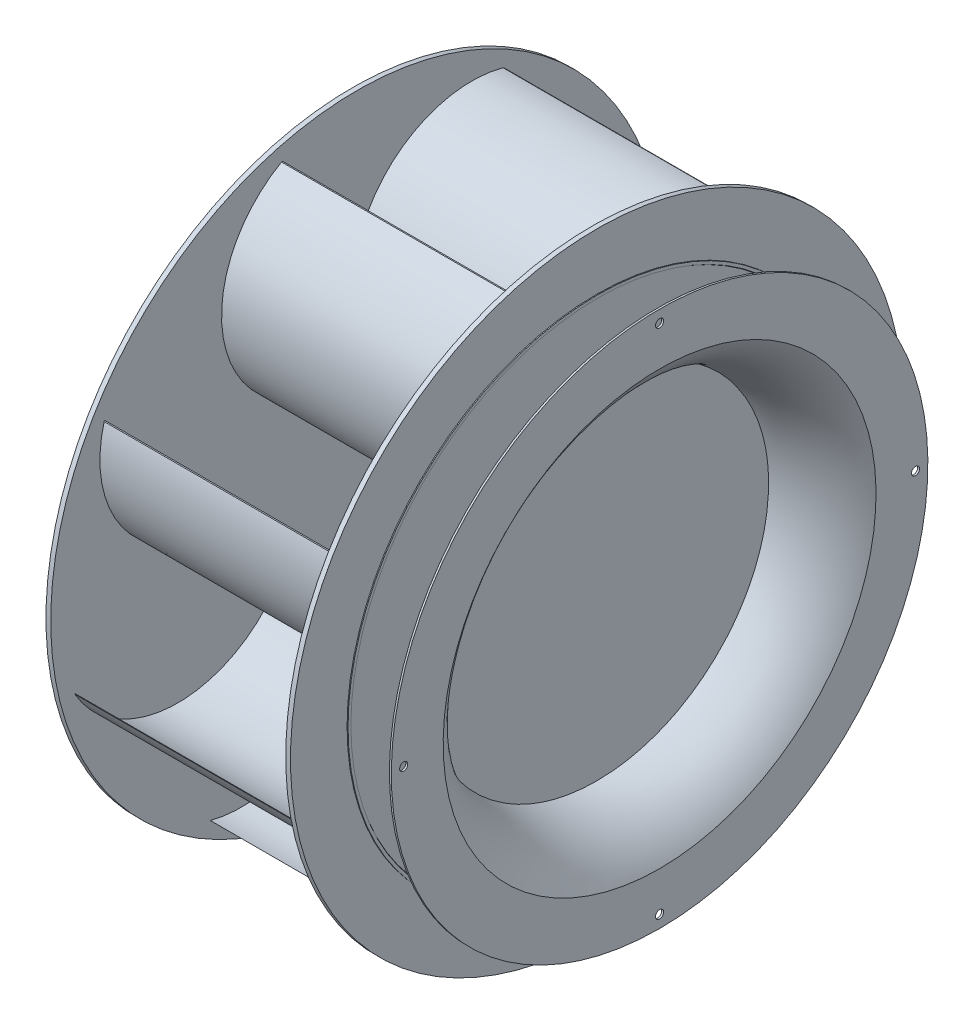
SolidWorks part; units mm, degrees
ref_plane "Front Plane" through (0, 0, 0) normal (0, 0, 1) x (1, 0, 0)
ref_plane "Top Plane" through (0, 0, 0) normal (0, 1, 0) x (1, 0, 0)
ref_plane "Right Plane" through (0, 0, 0) normal (1, 0, 0) x (0, 0, -1)
sketch "Sketch1" plane through (0, 0, 0) normal (0, 0, 1) x (1, 0, 0)
  line L0 (0, 0) -> (831.9083, 0) construction
  line L1 (0, 0) -> (0, 109)
  line L2 (5, 114) -> (70, 114)
  line L3 (70, 114) -> (70, 138)
  line L4 (70, 138) -> (90, 138)
  line L5 (90, 138) -> (90, 98)
  line L6 (90, 98) -> (95, 98)
  line L7 (95, 98) -> (95, 133)
  line L8 (95, 133) -> (105, 133)
  line L9 (105, 133) -> (105, 98)
  line L10 (105, 98) -> (129, 98)
  line L11 (129, 98) -> (129, 0)
  line L12 (129, 0) -> (0, 0)
  arc A0 (5, 114) -> (0, 109) centre (5, 109) ccw
  point P16 (0, 114)
  dimension "D10" = 5
  dimension "D1" = 114
  dimension "D2" = 24
  dimension "D3" = 70
  dimension "D4" = 40
  dimension "D5" = 35
  dimension "D6" = 5
  dimension "D7" = 20
  dimension "D8" = 10
  dimension "D9" = 59
revolve "Revolve1" add sketch "Sketch1" angle 360 about L0
sketch "Sketch2" plane through (129, 0, 0) normal (1, 0, 0) x (0, 0, -1)
  circle A0 centre (0, 0) radius 322
  dimension "D1" = 644
extrude "Extrude1" add sketch "Sketch2" along normal blind 5
sketch "Sketch9" plane through (129, 0, 0) normal (-1, 0, 0) x (0, 0, 1)
  circle A0 centre (0, 0) radius 317
  circle A1 centre (0, 0) radius 100
  circle A2 centre (0, 0) radius 322 construction
  dimension "D1" = 5
  dimension "D2" = 200
extrude "Extrude7" cut sketch "Sketch9" against normal blind 3
ref_plane "Plane1" through (381, 0, 0) normal (1, 0, 0) x (0, 0, -1)
sketch "Sketch3" plane through (381, 0, 0) normal (1, 0, 0) x (0, 0, -1)
  circle A0 centre (0, 0) radius 322
  dimension "D1" = 644
extrude "Extrude2" add sketch "Sketch3" along normal blind 5 separate body
sketch "Sketch4" plane through (134, 0, 0) normal (1, 0, 0) x (0, 0, -1)
  line L0 (0, 0) -> (0, 307) construction
  line L1 (0, 0) -> (161, 278.8602) construction
  line L2 (0, 112.5) -> (0.866, 112)
  line L3 (153.5, 265.8698) -> (154.366, 265.3698)
  circle A0 centre (0, 0) radius 307 construction
  circle A1 centre (0, 0) radius 322 construction
  circle A2 centre (0, 0) radius 112.5 construction
  arc A3 (0, 112.5) -> (153.5, 265.8698) centre (120.6282, 145.2694) cw
  arc A4 (0.866, 112) -> (154.366, 265.3698) centre (121.4942, 144.7694) cw
  dimension "D1" = 15
  dimension "D2" = 225
  dimension "D6" = 125
  dimension "D7" = 125
  dimension "D3" = 30
  dimension "D4" = 60
  dimension "D5" = 1
extrude "Extrude3" add sketch "Sketch4" along normal up to surface (252 mm away) up to face at (386, 0, -322)
ref_axis "Axis1" through (253.5503, 0, 0) along (-1, 0, 0)
pattern_circular "CirPattern1" count 8 over 360 about axis through (253.5503, 0, 0) along (-1, 0, 0) of "Extrude3"
sketch "Sketch5" plane through (0, 0, 0) normal (0, 0, 1) x (1, 0, 0)
  line L0 (0, 0) -> (527.2916, 0) construction
  line L1 (253.5503, 0) -> (75.411, 0) construction
  line L2 (386, 262.5) -> (387, 262.5)
  line L3 (387, 262.5) -> (387, 259.5)
  line L4 (386, 262.5) -> (386, 259.5)
  line L5 (354, 182.5) -> (354, 181.5)
  line L6 (70, 138) -> (70, -138) construction
  line L7 (386, -322) -> (386, 322) construction
  arc A0 (387, 259.5) -> (354, 182.5) centre (422.05, 198.9071) ccw
  arc A1 (386, 259.5) -> (354, 181.5) centre (421.7019, 199.2889) ccw
  dimension "D7" = 70
  dimension "D8" = 70
  dimension "D1" = 181.5
  dimension "D2" = 1
  dimension "D3" = 1
  dimension "D4" = 3
  dimension "D5" = 262.5
  dimension "D6" = 284
revolve "Revolve2" add sketch "Sketch5" angle 360 about L0
ref_plane "Plane3" through (452, 0, 0) normal (1, 0, 0) x (0, 0, -1)
sketch "Sketch6" plane through (0, 0, 0) normal (0, 0, 1) x (1, 0, 0)
  line L0 (452, 282) -> (450, 282)
  line L1 (452, -251.35) -> (452, 251.35) construction
  line L2 (450, 282) -> (450, 227.5)
  line L3 (0, 0) -> (615.1417, 0) construction
  line L4 (0, 114) -> (0, -114) construction
  line L5 (253.5503, 0) -> (75.411, 0) construction
  line L6 (452, 282) -> (452, 227.5)
  line L7 (348, 181.5) -> (352, 181.5)
  line L8 (348, 181.5) -> (348, 179.5)
  line L9 (348, 179.5) -> (352, 179.5)
  arc A0 (352, 181.5) -> (450, 227.5) centre (365.2724, 280.6153) ccw
  arc A1 (352, 179.5) -> (452, 227.5) centre (365.9922, 278.5163) ccw
  dimension "D7" = 100
  dimension "D8" = 100
  dimension "D1" = 282
  dimension "D2" = 2
  dimension "D3" = 227.5
  dimension "D4" = 104
  dimension "D5" = 181.5
  dimension "D6" = 4
revolve "Revolve3" add sketch "Sketch6" angle 360 about L3
sketch "Sketch7" plane through (452, 0, 0) normal (1, 0, 0) x (0, 0, -1)
  line L0 (0, 0) -> (0, 269) construction
  circle A0 centre (0, 0) radius 269 construction
  circle A1 centre (0, 269) radius 4.25
  dimension "D1" = 538
  dimension "D2" = 8.5
extrude "Extrude5" cut sketch "Sketch7" against normal blind 5
pattern_circular "CirPattern2" count 4 over 360 about axis through (253.5503, 0, 0) along (-1, 0, 0) of "Extrude5"
sketch "Sketch8" plane through (0, 0, 0) normal (1, 0, 0) x (0, 0, -1)
  line L0 (0, 0) -> (0, 126) construction
  circle A0 centre (0, 0) radius 126 construction
  circle A1 centre (0, 126) radius 5
  dimension "D1" = 252
  dimension "D2" = 10
extrude "Extrude6" cut sketch "Sketch8" along normal up to surface (90 mm away) up to face at (90, 0, 138)
pattern_circular "CirPattern3" count 8 over 360 about axis through (253.5503, 0, 0) along (-1, 0, 0) of "Extrude6"
